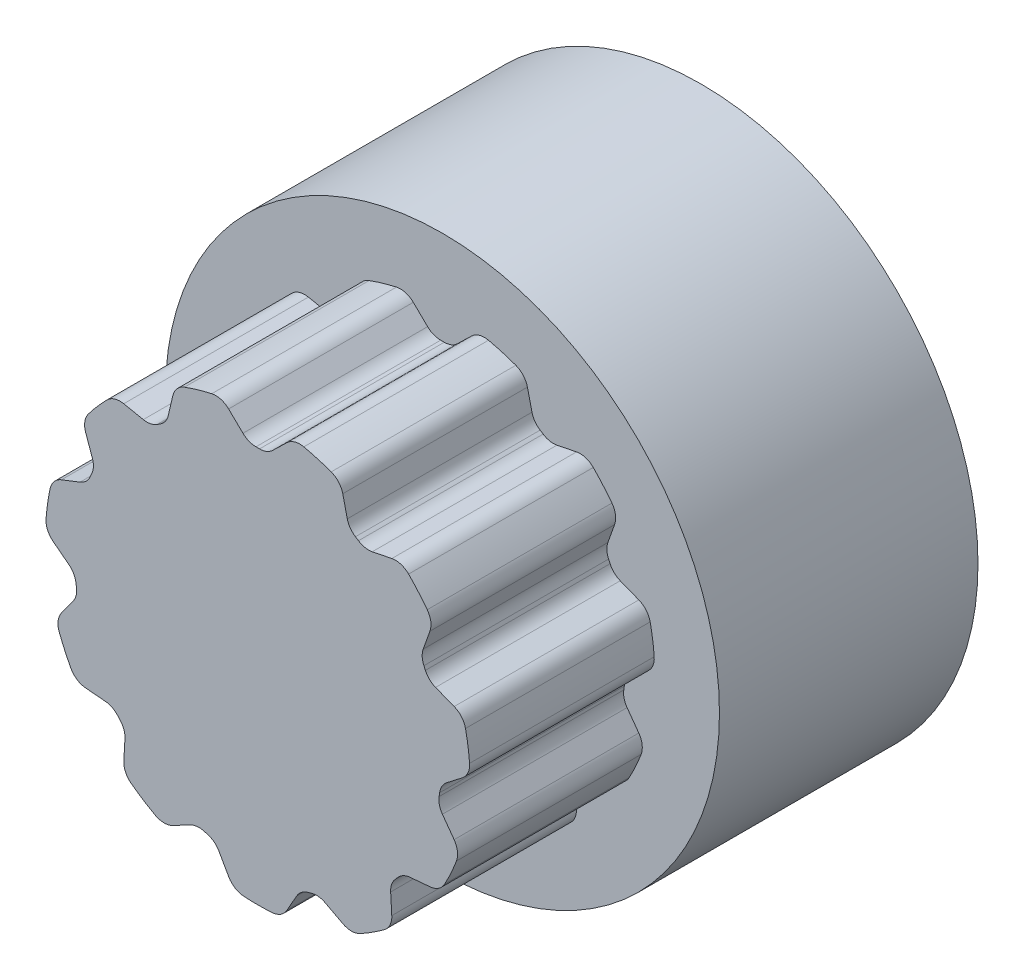
SolidWorks part; units mm, degrees
material "2024 Alloy"
ref_plane "Front Plane" through (0, 0, 0) normal (0, 0, 1) x (1, 0, 0)
ref_plane "Top Plane" through (0, 0, 0) normal (0, 1, 0) x (1, 0, 0)
ref_plane "Right Plane" through (0, 0, 0) normal (1, 0, 0) x (0, 0, -1)
sketch "Sketch2" plane through (0, 0, 0) normal (0, 0, 1) x (1, 0, 0)
  circle A1 centre (0, 0) radius 5.75
  dimension "D2" = 11.5
extrude "Boss-Extrude1" add sketch "Sketch2" along normal blind 5
sketch "Sketch3" plane through (0, 0, 0) normal (0, 0, -1) x (-1, 0, 0)
  circle A0 centre (0, 0) radius 7.5
  dimension "D1" = 15
extrude "Boss-Extrude2" add sketch "Sketch3" along normal blind 7 contours A0
sketch "Sketch7" plane through (0, 0, 5) normal (0, 0, 1) x (1, 0, 0)
  line L0 (-0.25, 4.9608) -> (0.25, 4.9608) construction
  line L1 (-0.25, 4.9608) -> (-1, 5.6878)
  line L2 (0.25, 4.9608) -> (1, 5.6878)
  line L3 (0, 4.9608) -> (0, 4.75) construction
  line L4 (0, 4.75) -> (-1.5096, 4.75) construction
  line L5 (0, 4.9608) -> (0, 5.775) construction
  line L6 (0, 5.775) -> (-1.4156, 5.775) construction
  line L7 (0, 0) -> (0, 4.75) construction
  arc A0 (-1, 5.6878) -> (1, 5.6878) centre (0, 0) cw
  arc A1 (-0.25, 4.9608) -> (0.25, 4.9608) centre (0, 0) cw
  circle A2 centre (0, 0) radius 4.75 construction
  circle A3 centre (0, 0) radius 5.775 construction
  circle A4 centre (0, 0) radius 5.75 construction
  dimension "D1" = 9.5
  dimension "D2" = 11.55
  dimension "D3" = 0.8142
  dimension "D4" = 2
  dimension "D5" = 0.5
extrude "Cut-Extrude2" cut sketch "Sketch7" against normal up to surface (5 mm away) up to face at (-5.75, 0, 0)
fillet "Fillet1" radius 0.5 4 edges at (0.9778, 5.6663, 2.5) (-0.9778, 5.6663, 2.5) (-0.25, 4.9608, 2.5) (0.25, 4.9608, 2.5)
pattern_circular "CirPattern2" count 11 over 360 about axis through (0, 0, 5) along (0, 0, -1) of "Cut-Extrude2", "Fillet1"
sketch "Sketch8" plane through (0, 0, -7) normal (0, 0, -1) x (-1, 0, 0)
  circle A0 centre (0, 0) radius 5.875
  dimension "D1" = 11.75
extrude "Cut-Extrude3" cut sketch "Sketch8" against normal blind 6
sketch "Sketch9" plane through (0, 0, -1) normal (0, 0, -1) x (-1, 0, 0)
  line L0 (-0.2, 5.0608) -> (0.2, 5.0608) construction
  line L1 (-0.2, 5.0608) -> (-0.95, 5.7977)
  line L2 (0.2, 5.0608) -> (0.95, 5.7977)
  line L3 (0, 5.0608) -> (0, 4.75) construction
  line L4 (0, 4.75) -> (-0.4187, 4.75) construction
  line L5 (0, 5.0608) -> (0, 5.875) construction
  line L6 (0, 5.875) -> (-0.3248, 5.875) construction
  line L7 (0, 0) -> (0, 4.75) construction
  arc A0 (-0.95, 5.7977) -> (0.95, 5.7977) centre (0, 0) cw
  arc A1 (-0.2, 5.0608) -> (0.2, 5.0608) centre (0, 0) cw
  circle A2 centre (0, 0) radius 4.75 construction
  circle A3 centre (0, 0) radius 5.875 construction
  dimension "D1" = 9.5
  dimension "D2" = 11.75
  dimension "D3" = 0.8142
  dimension "D4" = 1.9
  dimension "D5" = 0.4
extrude "Boss-Extrude3" add sketch "Sketch9" along normal up to surface (6 mm away) up to face at (-5.875, 0, -7)
fillet "Fillet2" radius 0.5 4 edges at (-0.95, 5.7977, -4) (-0.2, 5.0608, -4) (0.2, 5.0608, -4) (0.95, 5.7977, -4)
pattern_circular "CirPattern3" count 11 over 360 about axis through (0, 0, -1) along (0, 0, -1) of "Fillet2", "Boss-Extrude3"
